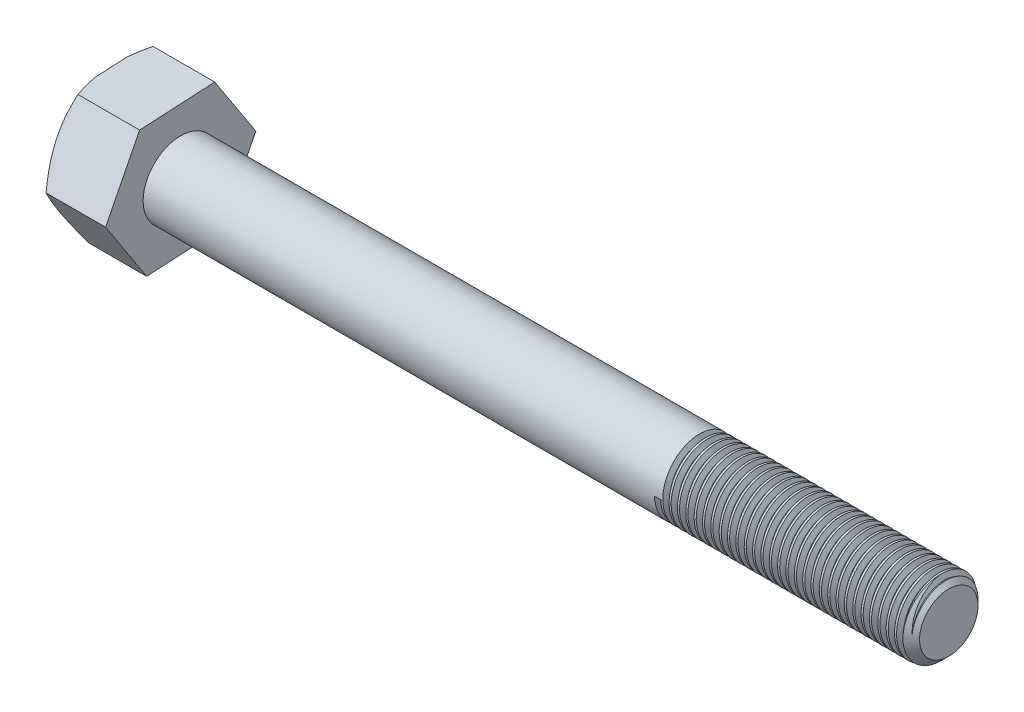
SolidWorks part; units mm, degrees
ref_plane "Front Plane" through (0, 0, 0) normal (0, 0, 1) x (1, 0, 0)
ref_plane "Top Plane" through (0, 0, 0) normal (0, 1, 0) x (1, 0, 0)
ref_plane "Right Plane" through (0, 0, 0) normal (1, 0, 0) x (0, 0, -1)
sketch "Sketch1" plane through (0, 0, 0) normal (1, 0, 0) x (0, 0, -1)
  line L1 (4.9192, -7.5522) -> (9, 0.484)
  line L2 (9, 0.484) -> (4.0808, 8.0362)
  line L3 (4.0808, 8.0362) -> (-4.9192, 7.5522)
  line L4 (-4.9192, 7.5522) -> (-9, -0.484)
  line L5 (-9, -0.484) -> (-4.0808, -8.0362)
  line L6 (-4.0808, -8.0362) -> (4.9192, -7.5522)
  circle A0 centre (0, 0) radius 4.5
  circle A1 centre (0, 0) radius 7.8055 construction
  dimension "D2" = 9
  dimension "D1" = 18
extrude "Boss-Extrude1" add sketch "Sketch1" along normal blind 8
extrude "Boss-Extrude2" add sketch "Sketch1<2>" along normal blind 100 contours A0 region at (0, 0, 0)
sketch "Sketch1<2>" plane through (0, 0, 0) normal (1, 0, 0) x (0, 0, -1) same geometry as "Sketch1"
sketch "Sketch8" plane through (0, 0, 0) normal (0, 0, 1) x (1, 0, 0)
  line L0 (-996, 0.484) -> (49004, 0.484) construction
  line L1 (8, 0.484) -> (0, 0.484) construction
  line L2 (0, 8.0362) -> (0, 12.9045)
  line L3 (0, 12.9045) -> (2.8107, 12.9045)
  line L4 (2.8107, 12.9045) -> (0, 8.0362)
  point P5 (4, 0.484)
  dimension "D1" = 30
revolve "Cut-Revolve1" cut sketch "Sketch8" angle 360 about L0
chamfer "Chamfer1" distance 1 angle 45 1 edges at (100, 0, -4.5)
thread "Thread1" pitch 1 method cut profile "Thread Profile1" start angle 0, offset 1, length 30, pitch 1, diameter 9
ref_plane "Plane1" through (100, 0, 4.5) normal (0, 1, 0) x (0, 0, -1)
sketch "Thread Profile1" plane through (100, 0, 4.5) normal (0, 1, 0) x (0, 0, -1)
  line L0 (0, 0) -> (0, 1) construction
  line L1 (0, 0) -> (0.5413, 0.3125)
  line L2 (0.5413, 0.3125) -> (0.5413, 0.4375)
  line L3 (0.5413, 0.4375) -> (0, 0.75)
  line L4 (0.5413, 0.375) -> (0, 0.375) construction
  line L11 (0, 0) -> (0, 0.75)
  point P2 (0, 0)
  dimension "Pitch" = 1
  dimension "Profile_Angle" = 60
  dimension "Profile_Land" = 0.125
  dimension "Profile_Height" = 0.5413
